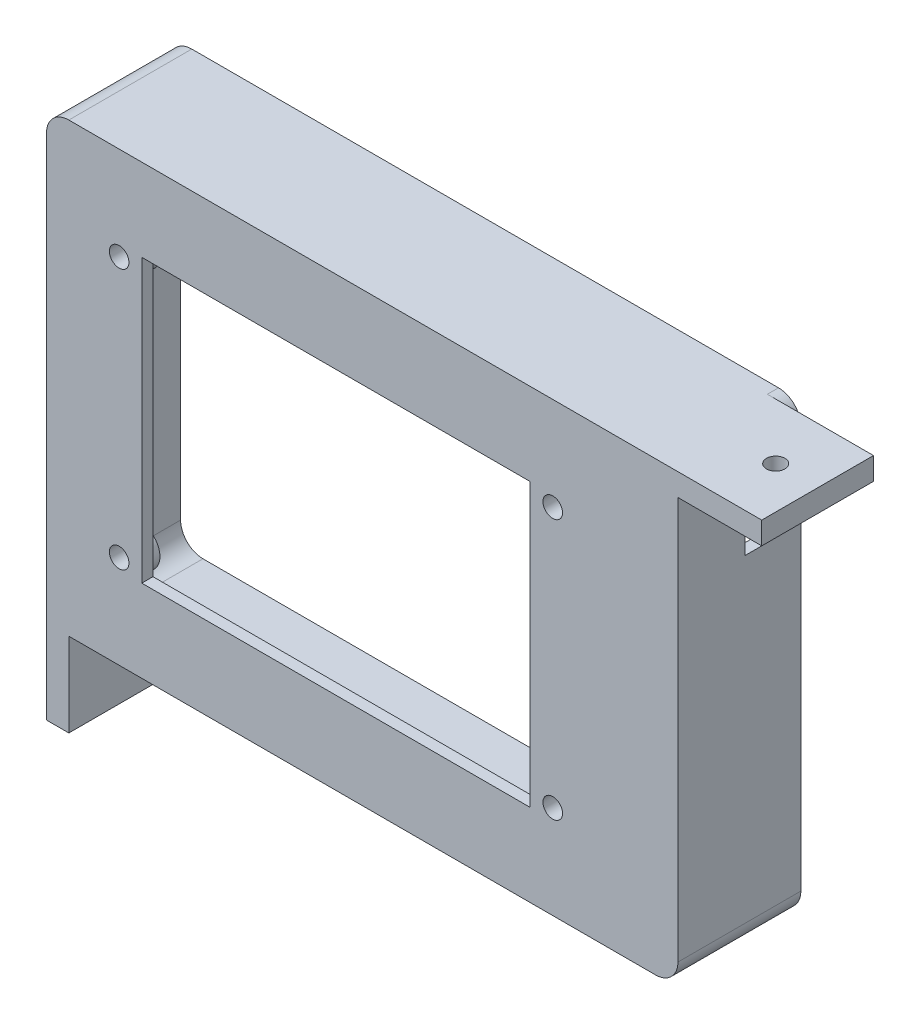
SolidWorks part; units mm, degrees
ref_plane "前视基准面" through (0, 0, 0) normal (0, 0, 1) x (1, 0, 0)
ref_plane "上视基准面" through (0, 0, 0) normal (0, 1, 0) x (1, 0, 0)
ref_plane "右视基准面" through (0, 0, 0) normal (1, 0, 0) x (0, 0, -1)
sketch "草图1" plane through (0, 0, 0) normal (0, 0, 1) x (1, 0, 0)
  line L1 (0, 0) -> (69.5, 0)
  line L2 (0, 0) -> (0, 50.5)
  line L3 (0, 50.5) -> (69.5, 50.5)
  line L4 (69.5, 0) -> (69.5, 50.5)
  line L5 (-17.05, 65.25) -> (95.95, 65.25)
  line L6 (-17.05, 65.25) -> (-17.05, -14.75)
  line L7 (-17.05, -14.75) -> (95.95, -14.75)
  line L8 (95.95, 65.25) -> (95.95, -14.75)
  circle A0 centre (-4.05, 48.55) radius 1.75
  circle A1 centre (73.55, 48.55) radius 1.75
  circle A2 centre (73.55, 1.95) radius 1.75
  circle A3 centre (-4.05, 1.95) radius 1.75
  point P10 (-17.05, 25.25)
  point P11 (0, 25.25)
  point P13 (34.75, 50.5)
  point P21 (69.5, 25.25)
  dimension "D9" = 3.5
  dimension "D1" = 50.5
  dimension "D2" = 69.5
  dimension "D3" = 113
  dimension "D4" = 80
  dimension "D5" = 46.6
  dimension "D6" = 77.6
  dimension "D7" = 38.8
  dimension "D8" = 23.3
  dimension "D10" = 13
extrude "凸台-拉伸1" add sketch "草图1" along normal blind 2
sketch "草图2" plane through (0, 0, 0) normal (0, 0, -1) x (-1, 0, 0)
  circle A0 centre (-73.55, 48.55) radius 3.5
  circle A1 centre (4.05, 48.55) radius 3.5
  circle A2 centre (4.05, 1.95) radius 3.5
  circle A3 centre (-73.55, 1.95) radius 3.5
  circle A5 centre (-73.55, 48.55) radius 1.75 construction
  circle A6 centre (4.05, 48.55) radius 1.75 construction
  circle A7 centre (4.05, 1.95) radius 1.75 construction
  circle A8 centre (-73.55, 1.95) radius 1.75 construction
  circle A9 centre (-73.55, 48.55) radius 1.75
  circle A10 centre (4.05, 48.55) radius 1.75
  circle A11 centre (4.05, 1.95) radius 1.75
  circle A12 centre (-73.55, 1.95) radius 1.75
  dimension "D1" = 7
extrude "凸台-拉伸2" add sketch "草图2" along normal blind 1.8
sketch "草图4" plane through (0, 0, 0) normal (0, 0, -1) x (-1, 0, 0)
  line L1 (-93.95, 63.25) -> (15.05, 63.25)
  line L2 (-93.95, 63.25) -> (-93.95, -12.75)
  line L3 (-93.95, -12.75) -> (15.05, -12.75)
  line L4 (17.05, -14.75) -> (17.05, 65.25)
  line L5 (17.05, 65.25) -> (-95.95, 65.25)
  line L6 (-95.95, 65.25) -> (-95.95, -14.75)
  line L7 (-95.95, -14.75) -> (17.05, -14.75)
  line L8 (17.05, -14.75) -> (17.05, 65.25)
  line L9 (17.05, 65.25) -> (-95.95, 65.25)
  line L10 (-95.95, 65.25) -> (-95.95, -14.75)
  line L11 (-95.95, -14.75) -> (17.05, -14.75)
  line L12 (15.05, 63.25) -> (15.05, -12.75)
  dimension "D2" = 2
  dimension "D3" = 2
  dimension "D4" = 2
  dimension "D5" = 2
  dimension "D1" = 0
extrude "凸台-拉伸3" add sketch "草图4" along normal blind 20
fillet "圆角1" radius 4 8 edges at (93.95, -12.75, -10) (93.95, 63.25, -10) (-15.05, 63.25, -10) (-15.05, -12.75, -10) (-17.05, 65.25, -9) (-17.05, -14.75, -9) (95.95, -14.75, -9) (95.95, 65.25, -9)
sketch "草图5" plane through (95.95, 0, 0) normal (1, 0, 0) x (0, 0, -1)
  line L0 (20, 61.25) -> (20, -10.75) construction
  line L1 (20, 61.25) -> (10, 61.25)
  line L2 (20, 61.25) -> (20, 46.25)
  line L3 (20, 46.25) -> (10, 46.25)
  line L4 (10, 61.25) -> (10, 46.25)
  line L5 (-2, 65.25) -> (20, 65.25) construction
  dimension "D1" = 15
  dimension "D2" = 4
  dimension "D3" = 10
extrude "切除-拉伸1" cut sketch "草图5" against normal blind 20
sketch "草图6" plane through (0, 0, 2) normal (0, 0, 1) x (1, 0, 0)
  line L0 (-17.05, -10.75) -> (-17.05, -29.75)
  line L1 (-17.05, -29.75) -> (-13.05, -29.75)
  line L2 (-13.05, -29.75) -> (-13.05, -14.75)
  line L3 (91.95, 65.25) -> (110.95, 65.25)
  line L4 (110.95, 65.25) -> (110.95, 61.25)
  line L5 (110.95, 61.25) -> (95.95, 61.25)
  arc A0 (-17.05, -10.75) -> (-13.05, -14.75) centre (-13.05, -10.75) ccw construction
  arc A1 (95.95, 61.25) -> (91.95, 65.25) centre (91.95, 61.25) ccw construction
  arc A2 (-17.05, -10.75) -> (-13.05, -14.75) centre (-13.05, -10.75) ccw
  arc A3 (95.95, 61.25) -> (91.95, 65.25) centre (91.95, 61.25) ccw
  dimension "D1" = 15
  dimension "D2" = 15
extrude "凸台-拉伸4" add sketch "草图6" against normal blind 20
sketch "草图7" plane through (-13.05, 0, 0) normal (1, 0, 0) x (0, 0, -1)
  circle A0 centre (8, -22.25) radius 1.65
  dimension "D1" = 3.3
extrude "切除-拉伸2" cut sketch "草图7" against normal blind 20
sketch "草图8" plane through (0, 61.25, 0) normal (0, -1, 0) x (1, 0, 0)
  circle A0 centre (103.45, -8) radius 1.65
  dimension "D1" = 3.3
extrude "切除-拉伸3" cut sketch "草图8" against normal blind 20
